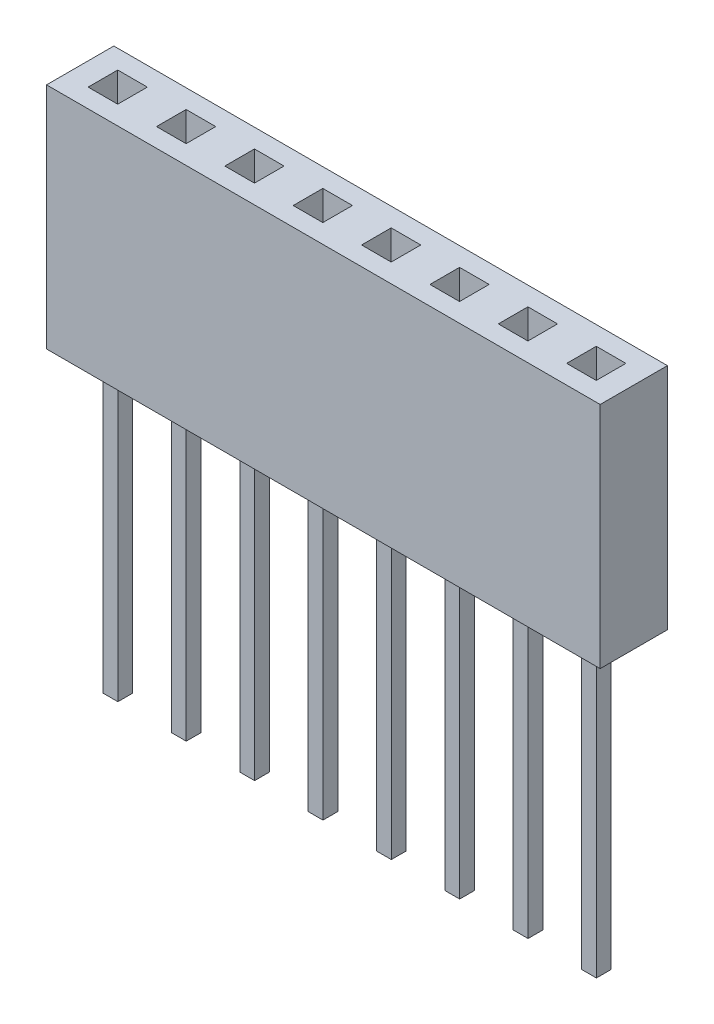
SolidWorks part; units mm, degrees
ref_plane "Front Plane" through (0, 0, 0) normal (0, 0, 1) x (1, 0, 0)
ref_plane "Top Plane" through (0, 0, 0) normal (0, 1, 0) x (1, 0, 0)
ref_plane "Right Plane" through (0, 0, 0) normal (1, 0, 0) x (0, 0, -1)
sketch "Sketch1" plane through (0, 0, 0) normal (0, 0, 1) x (1, 0, 0)
  line L1 (0, 0) -> (20.57, 0)
  line L2 (0, 0) -> (0, 8.5)
  line L3 (0, 8.5) -> (20.57, 8.5)
  line L4 (20.57, 0) -> (20.57, 8.5)
  dimension "D1" = 8.5
  dimension "D2" = 20.57
extrude "Boss-Extrude1" add sketch "Sketch1" along normal mid plane 2.5
sketch "Sketch2" plane through (0, 0, 0) normal (0, -1, 0) x (1, 0, 0)
  line L0 (0, 0) -> (20.57, 0) construction
  line L1 (20.57, 1.25) -> (20.57, -1.25) construction
  line L2 (3.385, -0.55) -> (4.485, -0.55)
  line L3 (0.845, -0.55) -> (1.945, -0.55)
  line L4 (0.845, -0.55) -> (0.845, 0.55)
  line L5 (0.845, 0.55) -> (1.945, 0.55)
  line L6 (1.945, -0.55) -> (1.945, 0.55)
  line L7 (0.845, -0.55) -> (1.945, 0.55) construction
  line L8 (0.845, 0.55) -> (1.945, -0.55) construction
  line L9 (3.385, -0.55) -> (3.385, 0.55)
  line L10 (3.385, 0.55) -> (4.485, 0.55)
  line L11 (4.485, -0.55) -> (4.485, 0.55)
  line L12 (3.385, -0.55) -> (4.485, 0.55) construction
  line L13 (3.385, 0.55) -> (4.485, -0.55) construction
  line L14 (5.925, -0.55) -> (7.025, -0.55)
  line L15 (5.925, -0.55) -> (5.925, 0.55)
  line L16 (5.925, 0.55) -> (7.025, 0.55)
  line L17 (7.025, -0.55) -> (7.025, 0.55)
  line L18 (5.925, -0.55) -> (7.025, 0.55) construction
  line L19 (5.925, 0.55) -> (7.025, -0.55) construction
  line L20 (8.465, -0.55) -> (9.565, -0.55)
  line L21 (8.465, -0.55) -> (8.465, 0.55)
  line L22 (8.465, 0.55) -> (9.565, 0.55)
  line L23 (9.565, -0.55) -> (9.565, 0.55)
  line L24 (8.465, -0.55) -> (9.565, 0.55) construction
  line L25 (8.465, 0.55) -> (9.565, -0.55) construction
  line L26 (11.005, -0.55) -> (12.105, -0.55)
  line L27 (11.005, -0.55) -> (11.005, 0.55)
  line L28 (11.005, 0.55) -> (12.105, 0.55)
  line L29 (12.105, -0.55) -> (12.105, 0.55)
  line L30 (11.005, -0.55) -> (12.105, 0.55) construction
  line L31 (11.005, 0.55) -> (12.105, -0.55) construction
  line L32 (13.545, -0.55) -> (14.645, -0.55)
  line L33 (13.545, -0.55) -> (13.545, 0.55)
  line L34 (13.545, 0.55) -> (14.645, 0.55)
  line L35 (14.645, -0.55) -> (14.645, 0.55)
  line L36 (13.545, -0.55) -> (14.645, 0.55) construction
  line L37 (13.545, 0.55) -> (14.645, -0.55) construction
  line L38 (16.085, -0.55) -> (17.185, -0.55)
  line L39 (16.085, -0.55) -> (16.085, 0.55)
  line L40 (16.085, 0.55) -> (17.185, 0.55)
  line L41 (17.185, -0.55) -> (17.185, 0.55)
  line L42 (16.085, -0.55) -> (17.185, 0.55) construction
  line L43 (16.085, 0.55) -> (17.185, -0.55) construction
  line L44 (18.625, -0.55) -> (19.725, -0.55)
  line L45 (18.625, -0.55) -> (18.625, 0.55)
  line L46 (18.625, 0.55) -> (19.725, 0.55)
  line L47 (19.725, -0.55) -> (19.725, 0.55)
  line L48 (18.625, -0.55) -> (19.725, 0.55) construction
  line L49 (18.625, 0.55) -> (19.725, -0.55) construction
  line L78 (1.395, 0) -> (3.935, 0) construction
  point P5 (1.395, 0)
  point P12 (3.935, 0)
  point P17 (6.475, 0)
  point P22 (9.015, 0)
  point P27 (11.555, 0)
  point P32 (14.095, 0)
  point P37 (16.635, 0)
  point P42 (19.175, 0)
  dimension "D1" = 1.1
  dimension "D3" = 1.395
  dimension "D4" = 2.54
  dimension "D2" = 8
extrude "Cut-Extrude1" cut sketch "Sketch2" against normal through all contours L3 L6 L5 L4 | L2 L11 L10 L9 | L14 L17 L16 L15 | L20 L23 L22 L21 | L26 L29 L28 L27 | L32 L35 L34 L33 | L38 L41 L40 L39 | L44 L47 L46 L45 region at (3.935, 0, 0) region at (1.395, 0, 0) region at (6.475, 0, 0) region at (9.015, 0, 0) region at (11.555, 0, 0) region at (14.095, 0, 0) region at (16.635, 0, 0) region at (19.175, 0, 0)
sketch "Sketch3" plane through (0, 0, 0) normal (0, -1, 0) x (1, 0, 0)
  line L1 (0, 1.25) -> (20.57, 1.25)
  line L2 (0, 1.25) -> (0, -1.25)
  line L3 (0, -1.25) -> (20.57, -1.25)
  line L4 (20.57, 1.25) -> (20.57, -1.25)
extrude "Boss-Extrude2" add sketch "Sketch3" against normal blind 1
sketch "Sketch4" plane through (0, 0, 0) normal (0, -1, 0) x (1, 0, 0)
  line L0 (1.125, 0) -> (1.675, 0) construction
  line L1 (1.125, 0.275) -> (1.675, 0.275)
  line L2 (1.125, 0.275) -> (1.125, -0.275)
  line L3 (1.125, -0.275) -> (1.675, -0.275)
  line L4 (1.675, 0.275) -> (1.675, -0.275)
  line L5 (0, 0) -> (20.57, 0) construction
  line L6 (20.57, 1.25) -> (20.57, -1.25) construction
  line L7 (0, 1.25) -> (0, -1.25) construction
  line L8 (3.665, 0.275) -> (3.665, -0.275)
  line L9 (3.665, 0.275) -> (4.215, 0.275)
  line L10 (3.665, -0.275) -> (4.215, -0.275)
  line L11 (4.215, 0.275) -> (4.215, -0.275)
  line L12 (6.205, 0.275) -> (6.205, -0.275)
  line L13 (6.205, 0.275) -> (6.755, 0.275)
  line L14 (6.205, -0.275) -> (6.755, -0.275)
  line L15 (6.755, 0.275) -> (6.755, -0.275)
  line L16 (8.745, 0.275) -> (8.745, -0.275)
  line L17 (8.745, 0.275) -> (9.295, 0.275)
  line L18 (8.745, -0.275) -> (9.295, -0.275)
  line L19 (9.295, 0.275) -> (9.295, -0.275)
  line L20 (11.285, 0.275) -> (11.285, -0.275)
  line L21 (11.285, 0.275) -> (11.835, 0.275)
  line L22 (11.285, -0.275) -> (11.835, -0.275)
  line L23 (11.835, 0.275) -> (11.835, -0.275)
  line L24 (13.825, 0.275) -> (13.825, -0.275)
  line L25 (13.825, 0.275) -> (14.375, 0.275)
  line L26 (13.825, -0.275) -> (14.375, -0.275)
  line L27 (14.375, 0.275) -> (14.375, -0.275)
  line L28 (16.365, 0.275) -> (16.365, -0.275)
  line L29 (16.365, 0.275) -> (16.915, 0.275)
  line L30 (16.365, -0.275) -> (16.915, -0.275)
  line L31 (16.915, 0.275) -> (16.915, -0.275)
  line L32 (18.905, 0.275) -> (18.905, -0.275)
  line L33 (18.905, 0.275) -> (19.455, 0.275)
  line L34 (18.905, -0.275) -> (19.455, -0.275)
  line L35 (19.455, 0.275) -> (19.455, -0.275)
  line L52 (1.125, 0.275) -> (3.665, 0.275) construction
  point P6 (1.4, 0)
  dimension "D1" = 0.55
  dimension "D2" = 1.4
  dimension "D4" = 2.54
  dimension "D3" = 8
extrude "Boss-Extrude3" add sketch "Sketch4" along normal blind 11 separate body
ref_axis "Axis1" through (1.395, 0, 0) along (0, -1, 0)
ref_axis "Axis2" through (19.175, 0, 0) along (0, -1, 0)
